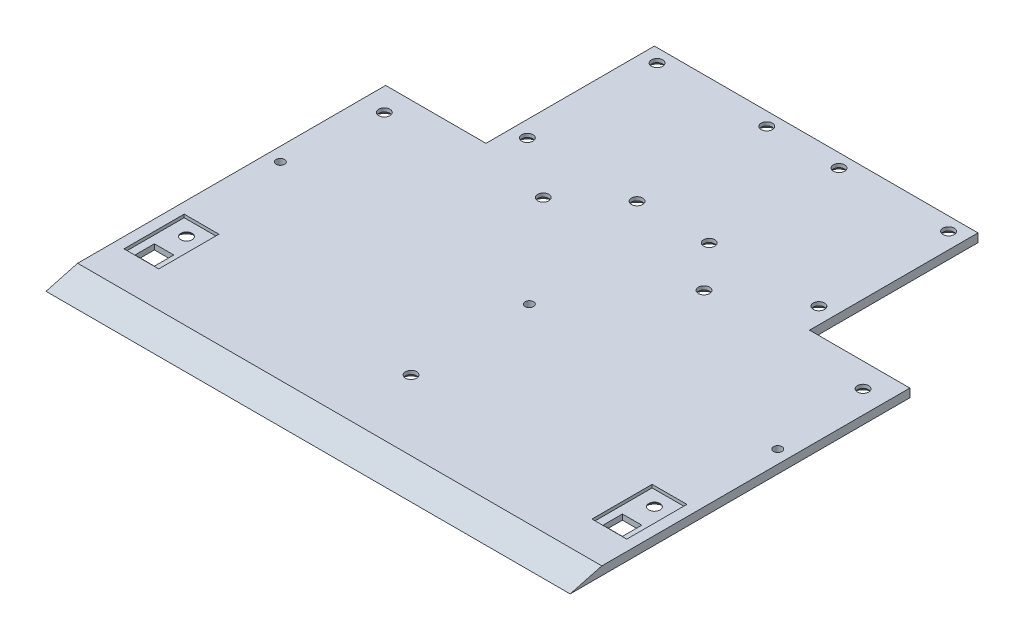
SolidWorks part; units mm, degrees
ref_plane "Alzado" through (0, 0, 0) normal (0, 0, 1) x (1, 0, 0)
ref_plane "Planta" through (0, 0, 0) normal (0, 1, 0) x (1, 0, 0)
ref_plane "Vista lateral" through (0, 0, 0) normal (1, 0, 0) x (0, 0, -1)
sketch "Croquis1" plane through (0, 0, 0) normal (1, 0, 0) x (0, 0, -1)
  line L0 (0, 0) -> (190, 0)
  line L1 (190, 0) -> (190, 3.17)
  line L2 (190, 3.17) -> (11.8306, 3.17)
  line L3 (0, 0) -> (11.8306, 3.17)
  dimension "D1" = 190
  dimension "D2" = 3.17
  dimension "D3" = 165
extrude "Saliente-Extruir1" add sketch "Croquis1" along normal blind 196
sketch "Croquis2" plane through (0, 0, 0) normal (0, -1, 0) x (-1, 0, 0)
  line L0 (0, 190) -> (0, 11.8306) construction
  line L1 (0, 127.0101) -> (-37.5, 127.0101)
  line L2 (0, 127.0101) -> (0, 190)
  line L3 (0, 190) -> (-37.5, 190)
  line L4 (-37.5, 127.0101) -> (-37.5, 190)
  line L5 (0, 127.0101) -> (-37.5, 190) construction
  line L6 (0, 190) -> (-37.5, 127.0101) construction
  line L7 (-196, 127.0101) -> (0, 127.0101) construction
  line L8 (-196, 190) -> (0, 190) construction
  line L9 (-37.5, 131.5) -> (-37.5, 190) construction
  point P4 (-18.75, 158.5051)
extrude "Cortar-Extruir1" cut sketch "Croquis2" against normal up to next
ref_plane "Plano1" through (98, 0, 0) normal (-1, 0, 0) x (0, 0, 1)
mirror "Simetría1" about plane through (98, 0, 0) normal (-1, 0, 0) of "Cortar-Extruir1"
sketch "Croquis3" plane through (0, 3.17, 0) normal (0, 1, 0) x (1, 0, 0)
  line L0 (196, 0) -> (0, 0) construction
  line L1 (4, 47.66) -> (17, 47.66)
  line L2 (4, 47.66) -> (4, 25.16)
  line L3 (4, 25.16) -> (17, 25.16)
  line L4 (17, 47.66) -> (17, 25.16)
  line L5 (4, 47.66) -> (17, 25.16) construction
  line L6 (4, 25.16) -> (17, 47.66) construction
  line L7 (0, 127.0101) -> (0, 11.8306) construction
  point P4 (10.5, 36.41)
  dimension "D1" = 25.16
  dimension "D2" = 22.5
  dimension "D3" = 13
  dimension "D4" = 4
extrude "Cortar-Extruir2" cut sketch "Croquis3" against normal blind 1.17
sketch "Croquis4" plane through (0, 2, 0) normal (0, 1, 0) x (1, 0, 0)
  line L0 (10.5, 25.16) -> (10.5, 26.41) construction
  line L1 (4, 25.16) -> (17, 25.16) construction
  line L2 (4, 26.41) -> (17, 26.41) construction
  line L3 (4, 47.66) -> (4, 25.16) construction
  line L4 (17, 25.16) -> (17, 47.66) construction
  line L5 (10.5, 26.41) -> (10.5, 33.66) construction
  line L6 (10.5, 30.035) -> (6.875, 30.035) construction
  line L7 (10.5, 30.035) -> (14.125, 30.035) construction
  line L8 (6.875, 30.035) -> (6.875, 26.41) construction
  line L9 (14.125, 30.035) -> (14.125, 33.66) construction
  dimension "D1" = 1.25
  dimension "D2" = 7.25
  dimension "D3" = 3.625
  dimension "D4" = 3.625
sketch "Croquis5" plane through (0, 2, 0) normal (0, 1, 0) x (1, 0, 0)
  line L1 (6.875, 26.41) -> (14.125, 26.41)
  line L2 (6.875, 26.41) -> (6.875, 33.66)
  line L3 (6.875, 33.66) -> (14.125, 33.66)
  line L4 (14.125, 26.41) -> (14.125, 33.66)
  line L5 (6.875, 26.41) -> (14.125, 33.66) construction
  line L6 (6.875, 33.66) -> (14.125, 26.41) construction
  point P4 (10.5, 30.035)
extrude "Cortar-Extruir3" cut sketch "Croquis5" against normal up to next
sketch "Croquis6" plane through (0, 2, 0) normal (0, 1, 0) x (1, 0, 0)
  line L0 (10.5, 47.66) -> (10.5, 46.41) construction
  line L1 (17, 47.66) -> (4, 47.66) construction
  line L2 (10.5, 46.41) -> (17, 46.41) construction
  line L3 (17, 25.16) -> (17, 47.66) construction
  line L4 (17, 46.41) -> (4, 46.41) construction
  line L5 (4, 47.66) -> (4, 25.16) construction
  circle A0 centre (10.5, 42.01) radius 1.6
  dimension "D2" = 3.2
  dimension "D1" = 1.25
  dimension "D3" = 4.4
extrude "Cortar-Extruir4" cut sketch "Croquis6" against normal up to next
mirror "Simetría2" about plane through (98, 0, 0) normal (-1, 0, 0) of "Cortar-Extruir2", "Cortar-Extruir4", "Cortar-Extruir3"
sketch "Sketch1" plane through (0, 3.17, 0) normal (0, 1, 0) x (1, 0, 0)
  circle A0 centre (8.5, 118.0101) radius 1.585
  circle A1 centre (187.5, 118.0101) radius 1.585
extrude "Cut-Extrude1" cut sketch "Sketch1" against normal up to next
sketch "Sketch2" plane through (0, 3.17, 0) normal (0, 1, 0) x (1, 0, 0)
  circle A0 centre (98.5, 38.0101) radius 1.585
extrude "Cut-Extrude2" cut sketch "Sketch2" against normal up to next
sketch "Sketch3" plane through (0, 3.17, 0) normal (0, 1, 0) x (1, 0, 0)
  circle A0 centre (43.5, 185) radius 1.5799
  circle A1 centre (84.5, 185) radius 1.585
  circle A2 centre (152.5, 185) radius 1.585
  circle A3 centre (111.5, 185) radius 1.585
  circle A4 centre (111.5, 136.5) radius 1.585
  circle A5 centre (152.5, 136.5) radius 1.585
  circle A6 centre (84.5, 136.5) radius 1.585
  circle A7 centre (43.5, 136.5) radius 1.585
extrude "Cut-Extrude3" cut sketch "Sketch3" against normal up to next
sketch "Sketch4" plane through (0, 3.17, 0) normal (0, 1, 0) x (1, 0, 0)
  circle A0 centre (65.7764, 120.1669) radius 1.6
  circle A1 centre (125.8764, 120.1669) radius 1.6
extrude "Cut-Extrude4" cut sketch "Sketch4" against normal blind 4.9
hole_wizard "Avellanado para tornillo con cabeza avellanada en cruz de M3.51" positions "3DSketch1" profile "Sketch5" countersink size "M3.5" standard "AS"
sketch3d "3DSketch1"
  line L0 (187.5, 0, -118.0101) -> (187.5, 3.17, -118.0101) construction
  line L1 (152.5, 0, -136.5) -> (152.5, 3.17, -136.5) construction
  line L2 (125.8764, 0, -120.1669) -> (125.8764, 3.17, -120.1669) construction
  line L3 (111.5, 0, -136.5) -> (111.5, 3.17, -136.5) construction
  line L4 (84.5, 0, -136.5) -> (84.5, 3.17, -136.5) construction
  line L5 (65.7764, 0, -120.1669) -> (65.7764, 3.17, -120.1669) construction
  line L6 (43.5, 0, -136.5) -> (43.5, 3.17, -136.5) construction
  line L7 (8.5, 0, -118.0101) -> (8.5, 3.17, -118.0101) construction
  line L8 (43.5, 0, -185) -> (43.5, 3.17, -185) construction
  line L9 (84.5, 0, -185) -> (84.5, 3.17, -185) construction
  line L10 (111.5, 0, -185) -> (111.5, 3.17, -185) construction
  line L11 (152.5, 0, -185) -> (152.5, 3.17, -185) construction
  line L12 (10.5, 0, -42.01) -> (10.5, 2, -42.01) construction
  line L13 (98.5, 0, -38.0101) -> (98.5, 3.17, -38.0101) construction
  line L14 (185.5, 0, -42.01) -> (185.5, 2, -42.01) construction
  point P0 (187.5, 0, -118.0101)
  point P4 (152.5, 0, -136.5)
  point P8 (125.8764, 0, -120.1669)
  point P12 (111.5, 0, -136.5)
  point P16 (84.5, 0, -136.5)
  point P20 (65.7764, 0, -120.1669)
  point P24 (43.5, 0, -136.5)
  point P28 (8.5, 0, -118.0101)
  point P32 (43.5, 0, -185)
  point P36 (84.5, 0, -185)
  point P40 (111.5, 0, -185)
  point P44 (152.5, 0, -185)
  point P48 (10.5, 0, -42.01)
  point P52 (98.5, 0, -38.0101)
  point P56 (185.5, 0, -42.01)
sketch "Sketch5" plane through (187.5, 0, -118.0101) normal (1, 0, 0) x (0, 0, -1)
  line L0 (0, 0) -> (0, 11.2618)
  line L1 (0, 11.2618) -> (2.1, 10)
  line L2 (2.1, 10) -> (2.1, 1.8348)
  line L3 (2.1, 1.8348) -> (4, 0)
  line L5 (4, 0) -> (0, 0)
  line L6 (-2.1, 1.8348) -> (-4, 0) construction
  line L10 (0, 11.2618) -> (-2.1, 10) construction
  line L11 (0, -6.35) -> (0, 107.95) construction
  dimension "Diámetro de taladro" = 4.2
  dimension "Profundidad de taladro" = 10
  dimension "Ángulo de avellanado cercano" = 8
  dimension "Ángulo de avellanado lejano" = 92
  dimension "Ángulo de perforador" = 118
sketch "Sketch6" plane through (0, 3.17, 0) normal (0, 1, 0) x (1, 0, 0)
  circle A0 centre (191.0671, 82.5578) radius 1.585
  circle A1 centre (97.6819, 83.0385) radius 1.585
  circle A2 centre (5.0671, 82.5578) radius 1.585
extrude "Cut-Extrude5" cut sketch "Sketch6" against normal blind 10
